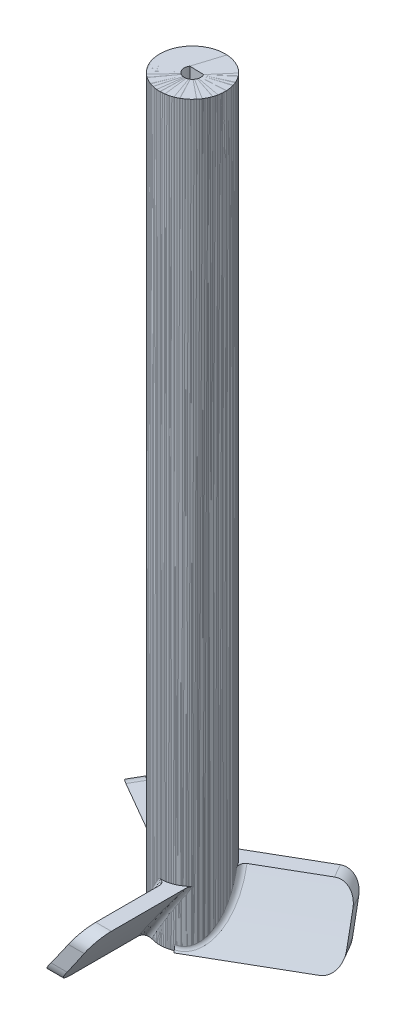
SolidWorks part; units mm, degrees
ref_plane "Front Plane" through (0, 0, 0) normal (0, 0, 1) x (1, 0, 0)
ref_plane "Top Plane" through (0, 0, 0) normal (0, 1, 0) x (1, 0, 0)
ref_plane "Right Plane" through (0, 0, 0) normal (1, 0, 0) x (0, 0, -1)
sketch "Sketch7" plane through (0, 0, 0) normal (0, 0, 1) x (1, 0, 0)
  line L0 (14.5391, 0) -> (-14.5391, 0) construction
  line L1 (6.849, 7) -> (4.9497, 7)
  line L2 (0, 0) -> (2, 0)
  arc A0 (0, 0) -> (4.9497, 7) centre (-91.3778, 69.8639) ccw
  arc A1 (6.849, 7) -> (2, 0) centre (-91.3778, 69.8639) cw
  dimension "D2" = 7
extrude "Boss-Extrude2" add sketch "Sketch7" along normal blind 15 contours A0 L1 A1 L2
fillet "Fillet1" radius 2 2 edges at (1, 0, 15) (5.8994, 7, 15)
sketch "Sketch10" plane through (0, 0, 0) normal (0, 1, 0) x (1, 0, 0)
  line L0 (0.3156, 0) -> (8.1957, 0) construction
  line L1 (4.9497, 0) -> (0, 0) construction
  line L2 (6.849, 0) -> (4.9497, 0) construction
  line L3 (2, 0) -> (6.849, 0) construction
  line L4 (4.2556, 0) -> (4.2556, -0.5251)
  line L5 (3.1481, -1000) -> (3.1481, 49000) construction
  circle A0 centre (4.2556, -0.5251) radius 3.9749
  point P5 (3.1481, 0)
  point P10 (-1.8519, 0)
  point P17 (3.1481, 0)
  dimension "D4" = 5
extrude "Boss-Extrude3" add sketch "Sketch10" along normal blind 90 contours A0 region at (0.3932, 0, 0.5251)
fillet "Fillet4" radius 0.7 2 edges at (1.2681, 1.6905, 3.147) (3.7358, 2.3821, 4.4659)
pattern_circular "CirPattern1" count 3 over 360 about axis through (4.2556, 90, 0.5251) along (0, -1, 0) of bodies 103 102
sketch "Sketch11" plane through (0, 90, 0) normal (0, 1, 0) x (1, 0, 0)
  line L0 (3.4046, 0) -> (5.1359, -0.0507)
  arc A1 (3.4046, 0) -> (5.1359, -0.0507) centre (4.2556, -0.5251) ccw
  circle A2 centre (4.2556, -0.5251) radius 3.9749 construction
extrude "Cut-Extrude1" cut sketch "Sketch11" against normal blind 40 contours A1 L0
equation "\"insidebladediameter\"=0.01"
equation "\"height\"= 0.007"
equation "\"bladethickness\"=0.002"
equation "\"insidebladeradius\"= \"insidebladediameter\" / 2"
equation "\"D1@Sketch7\"=\"bladethickness\""
equation "\"D2@Sketch7\"=\"height\""
equation "\"bladewidth\"= \"height\" * cos ( \"bladeangle\" )"
equation "\"bladelength\"= 0.015"
equation "\"D1@Boss-Extrude2\"=\"bladelength\""
equation "\"bladetipradius\"= 0.002"
equation "\"D1@Fillet1\"=\"bladetipradius\""
equation "\"fusedistance\"= 0.0045"
equation "\"motorrodheight\"=0.09"
equation "\"D1@Boss-Extrude3\"=\"motorrodheight\""
equation "\"numberofblades\"= 3"
equation "\"D1@CirPattern1\"=\"numberofblades\""
equation "\"roddiameter\"= ( \"bladewidth\" + 0.003 )"
equation "\"roddepth\"= 0.005"
equation "\"bladeangle\"= 45deg"
equation "\"m\"=1"
equation "\"flatfacedist\"= 0.0005"
equation "\"motorshaftdiameter\"=0.002"
equation "\"D1@Sketch11\"=\"motorshaftdiameter\"/2"
equation "\"D3@Sketch7\"=\"bladewidth\""
equation "\"D2@Sketch10\"=\"roddiameter\"/2-\"fusedistance\""
equation "\"D1@Sketch10\"=\"roddiameter\""
equation "\"D2@Sketch11\"=\"flatfacedist\""
equation "\"bladefilletradius\"= 0.0007"
equation "\"D1@Fillet4\"=\"bladefilletradius\""
